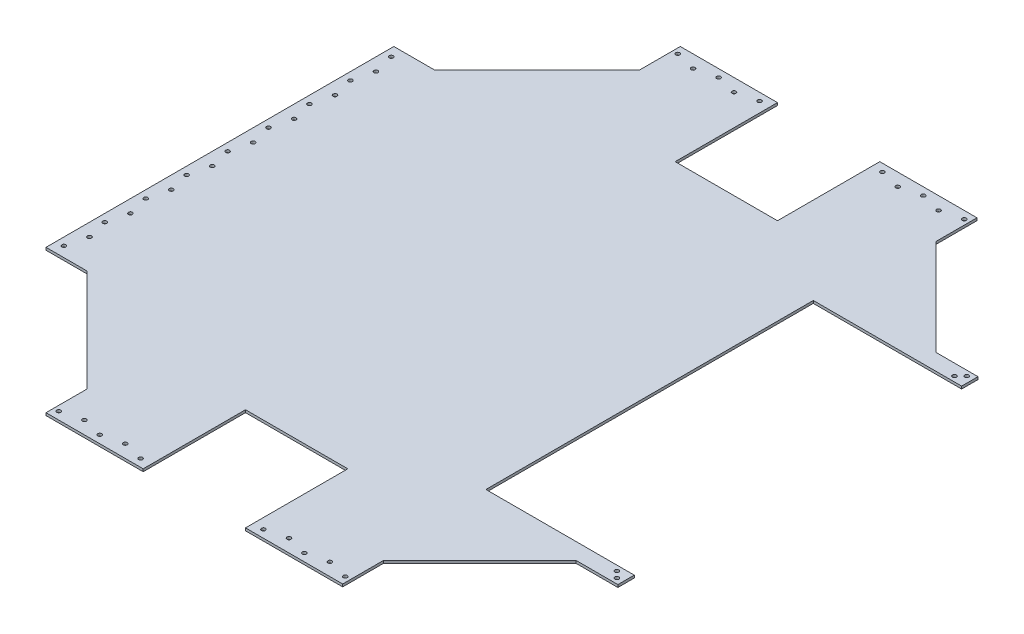
SolidWorks part; units mm, degrees
material "6061-T6 (SS)"
ref_plane "Front Plane" through (0, 0, 0) normal (0, 0, 1) x (1, 0, 0)
ref_plane "Top Plane" through (0, 0, 0) normal (0, 1, 0) x (1, 0, 0)
ref_plane "Right Plane" through (0, 0, 0) normal (1, 0, 0) x (0, 0, -1)
sketch "Sketch1" plane through (0, 0, 0) normal (0, 1, 0) x (1, 0, 0)
  line L0 (127, 393.7) -> (368.3, 152.4)
  line L1 (-139.7, -393.7) -> (127, -393.7)
  line L2 (-368.3, -165.1) -> (-368.3, 165.1)
  line L3 (-139.7, 393.7) -> (127, 393.7)
  line L4 (368.3, -152.4) -> (368.3, 152.4)
  line L5 (-368.3, -393.7) -> (368.3, 393.7) construction
  line L6 (-368.3, 393.7) -> (368.3, -393.7) construction
  line L7 (-368.3, 165.1) -> (-139.7, 393.7)
  line L8 (-368.3, -165.1) -> (-139.7, -393.7)
  line L9 (127, -393.7) -> (368.3, -152.4)
  point P0 (0, 0)
  dimension "D1" = 736.6
  dimension "D2" = 787.4
extrude "Boss-Extrude1" add sketch "Sketch1" along normal blind 3.175
sketch "Sketch2" plane through (0, 3.175, 0) normal (0, 1, 0) x (1, 0, 0)
  line L23 (368.3, -203.2) -> (165.1, -203.2)
  line L24 (368.3, -152.4) -> (368.3, 152.4) construction
  line L25 (165.1, -203.2) -> (165.1, 203.2)
  line L26 (165.1, 203.2) -> (368.3, 203.2)
  line L27 (368.3, 203.2) -> (368.3, -203.2)
  point P1 (368.3, 0)
  point P7 (368.3, 0)
  dimension "D1" = 406.4
  dimension "D2" = 203.2
extrude "Intake Cutout" cut sketch "Sketch2" against normal blind 3.175
sketch "Sketch3" plane through (0, 3.175, 0) normal (0, 1, 0) x (1, 0, 0)
  line L0 (-69.85, 393.7) -> (-69.85, 266.7)
  line L1 (127, 393.7) -> (-139.7, 393.7) construction
  line L2 (-69.85, 266.7) -> (57.15, 266.7)
  line L3 (57.15, 266.7) -> (57.15, 393.7)
  line L4 (57.15, 393.7) -> (-69.85, 393.7)
  line L5 (-139.7, -393.7) -> (127, -393.7) construction
  line L6 (-69.85, -393.7) -> (57.15, -393.7)
  line L7 (57.15, -393.7) -> (57.15, -266.7)
  line L8 (57.15, -266.7) -> (-69.85, -266.7)
  line L9 (-69.85, -266.7) -> (-69.85, -393.7)
  point P10 (-6.35, -393.7)
  point P13 (-6.35, -393.7)
  point P14 (-6.35, 393.7)
  point P15 (-6.35, 393.7)
  dimension "D1" = 127
  dimension "D2" = 127
extrude "Climber Cutout" cut sketch "Sketch3" against normal blind 3.175
sketch "Sketch7" plane through (0, 3.175, 0) normal (0, 1, 0) x (1, 0, 0)
  line L0 (317.5, 203.2) -> (349.25, 203.2)
  line L1 (349.25, 203.2) -> (349.25, 223.52)
  line L2 (349.25, 223.52) -> (297.18, 223.52)
  line L3 (317.5, 203.2) -> (127, 393.7) construction
  line L4 (297.18, 223.52) -> (317.5, 203.2)
  line L5 (317.5, -203.2) -> (349.25, -203.2)
  line L6 (349.25, -203.2) -> (349.25, -223.52)
  line L7 (349.25, -223.52) -> (297.18, -223.52)
  line L8 (127, -393.7) -> (317.5, -203.2) construction
  line L9 (297.18, -223.52) -> (317.5, -203.2)
  line L10 (-368.3, 165.1) -> (-368.3, 215.9)
  line L11 (-368.3, 215.9) -> (-317.5, 215.9)
  line L12 (-139.7, 393.7) -> (-368.3, 165.1) construction
  line L13 (-317.5, 215.9) -> (-368.3, 165.1)
  line L14 (-139.7, 393.7) -> (-190.5, 393.7)
  line L15 (-190.5, 393.7) -> (-190.5, 342.9)
  line L16 (-190.5, 342.9) -> (-139.7, 393.7)
  line L17 (127, 393.7) -> (177.8, 393.7)
  line L18 (177.8, 393.7) -> (177.8, 342.9)
  line L19 (177.8, 342.9) -> (127, 393.7)
  line L20 (177.8, -342.9) -> (177.8, -393.7)
  line L21 (177.8, -393.7) -> (127, -393.7)
  line L22 (-139.7, -393.7) -> (-190.5, -393.7)
  line L23 (-190.5, -393.7) -> (-190.5, -342.9)
  line L24 (-368.3, -165.1) -> (-139.7, -393.7) construction
  line L25 (-190.5, -342.9) -> (-139.7, -393.7)
  line L26 (-368.3, -165.1) -> (-368.3, -215.9)
  line L27 (-368.3, -215.9) -> (-317.5, -215.9)
  line L28 (-317.5, -215.9) -> (-368.3, -165.1)
  line L29 (177.8, -342.9) -> (127, -393.7)
  dimension "D1" = 20.32
  dimension "D2" = 31.75
  dimension "D3" = 50.8
  dimension "D4" = 50.8
extrude "Boss-Extrude3" add sketch "Sketch7" against normal up to surface (3.175 mm away) up to face at (8.4667, 0, 0)
hole_wizard "3/16 (0.195) Diameter Hole1" positions "Sketch5" profile "Sketch6" hole size "3/16" standard "ANSI Inch" end condition through all
sketch "Sketch5" plane through (0, 3.175, 0) normal (0, 1, 0) x (1, 0, 0)
  line L1 (-69.85, 393.7) -> (-190.5, 393.7) construction
  line L12 (349.25, 203.2) -> (165.1, 203.2) construction
  line L15 (349.25, 203.2) -> (349.25, 223.52) construction
  line L16 (-1.7463, 0) -> (1.7463, 0) construction
  line L17 (-190.5, 393.7) -> (-190.5, 342.9) construction
  line L18 (-368.3, 215.9) -> (-368.3, -215.9) construction
  line L19 (-368.3, -215.9) -> (-317.5, -215.9) construction
  point P4 (-133.35, 384.175)
  point P6 (-107.95, 377.825)
  point P13 (-82.55, 384.175)
  point P14 (-82.55, 384.175)
  point P16 (-82.55, 384.175)
  point P43 (-57.15, 377.825)
  point P44 (-31.75, 384.175)
  point P46 (-6.35, 377.825)
  point P47 (19.05, 384.175)
  point P49 (44.45, 377.825)
  point P50 (69.85, 384.175)
  point P52 (95.25, 377.825)
  point P53 (120.65, 384.175)
  point P55 (146.05, 377.825)
  point P56 (171.45, 384.175)
  point P64 (-82.55, 384.175)
  point P66 (-31.75, 384.175)
  point P68 (19.05, 384.175)
  point P70 (69.85, 384.175)
  point P72 (120.65, 384.175)
  point P74 (171.45, 384.175)
  point P76 (222.25, 384.175)
  point P330 (361.95, -170.9053)
  point P382 (196.85, 377.825)
  point P411 (341.63, 217.17)
  point P413 (334.01, 209.55)
  point P435 (334.01, -209.55)
  point P436 (341.63, -217.17)
  point P446 (-158.75, 377.825)
  point P448 (-184.15, 384.175)
  point P462 (-184.15, -384.175)
  point P463 (-158.75, -377.825)
  point P464 (171.45, -384.175)
  point P465 (146.05, -377.825)
  point P466 (120.65, -384.175)
  point P467 (95.25, -377.825)
  point P468 (69.85, -384.175)
  point P469 (44.45, -377.825)
  point P470 (19.05, -384.175)
  point P471 (-6.35, -377.825)
  point P472 (-31.75, -384.175)
  point P473 (-57.15, -377.825)
  point P474 (-82.55, -384.175)
  point P475 (-107.95, -377.825)
  point P476 (-133.35, -384.175)
  point P557 (-358.775, 101.6)
  point P559 (-358.775, 50.8)
  point P561 (-358.775, 0)
  point P563 (-358.775, -50.8)
  point P565 (-358.775, -101.6)
  point P571 (-358.775, -203.2)
  point P573 (-352.425, -177.8)
  point P575 (-358.775, -152.4)
  point P577 (-352.425, -127)
  point P612 (-358.775, -101.6)
  point P613 (-352.425, -76.2)
  point P616 (-358.775, -50.8)
  point P617 (-352.425, -25.4)
  point P620 (-358.775, 0)
  point P621 (-352.425, 25.4)
  point P624 (-358.775, 50.8)
  point P625 (-352.425, 76.2)
  point P628 (-358.775, 101.6)
  point P629 (-352.425, 127)
  point P632 (-358.775, 152.4)
  point P633 (-352.425, 177.8)
  point P636 (-358.775, 203.2)
  point P638 (-358.775, -91.4878)
  point P639 (-358.775, -100.7738)
  point P640 (0, 0)
  point P641 (-358.775, -101.6)
  point P642 (0, 0)
  point P643 (-352.425, -76.2)
  point P644 (0, 0)
  point P645 (-352.425, -127)
  point P646 (0, 0)
  point P647 (-358.775, -152.4)
  point P648 (0, 0)
  point P649 (-358.775, -50.8)
  point P650 (0, 0)
  point P651 (-352.425, -25.4)
  point P652 (0, 0)
  point P653 (-358.775, 0)
  point P654 (0, 0)
  point P655 (-352.425, 25.4)
  point P656 (0, 0)
  point P657 (-358.775, 50.8)
  point P658 (0, 0)
  point P659 (-352.425, 76.2)
  point P660 (0, 0)
  point P661 (-358.775, 101.6)
  point P662 (0, 0)
  point P663 (-352.425, 127)
  point P664 (0, 0)
  point P665 (-358.775, 152.4)
  point P666 (0, 0)
  point P667 (-352.425, 177.8)
  point P668 (-358.775, -106.0431)
  point P669 (-358.775, -110.8418)
  point P672 (0, 0)
  point P673 (-352.425, 228.6)
  dimension "D1" = 25.4
  dimension "D2" = 25.4
  dimension "D3" = 9.525
  dimension "D4" = 15.875
  dimension "D5" = 6.35
  dimension "D7" = 50.8
  dimension "D9" = 25.4
  dimension "D10" = 25.4
  dimension "D11" = 15.875
  dimension "D12" = 9.525
  dimension "D13" = 7.62
  dimension "D14" = 7.62
  dimension "D15" = 25.4
  dimension "D16" = 6.35
  dimension "D17" = 7.62
  dimension "D18" = 25.4
  dimension "D19" = 12.7
  dimension "D8" = 25.4
  dimension "D20" = 8
  dimension "D21" = 25.4
  dimension "D6" = 7
sketch "Sketch6" plane through (-133.35, 3.175, -384.175) normal (1, 0, 0) x (0, 0, 1)
  line L0 (0, 0) -> (0, 3.175)
  line L1 (0, 3.175) -> (2.4765, 3.175)
  line L2 (2.4765, 3.175) -> (2.4765, 0)
  line L5 (2.4765, 0) -> (0, 0)
  line L11 (0, -6.35) -> (0, 107.95) construction
  dimension "Thru Hole Dia." = 4.953
  dimension "Thru Hole Depth" = 3.175
